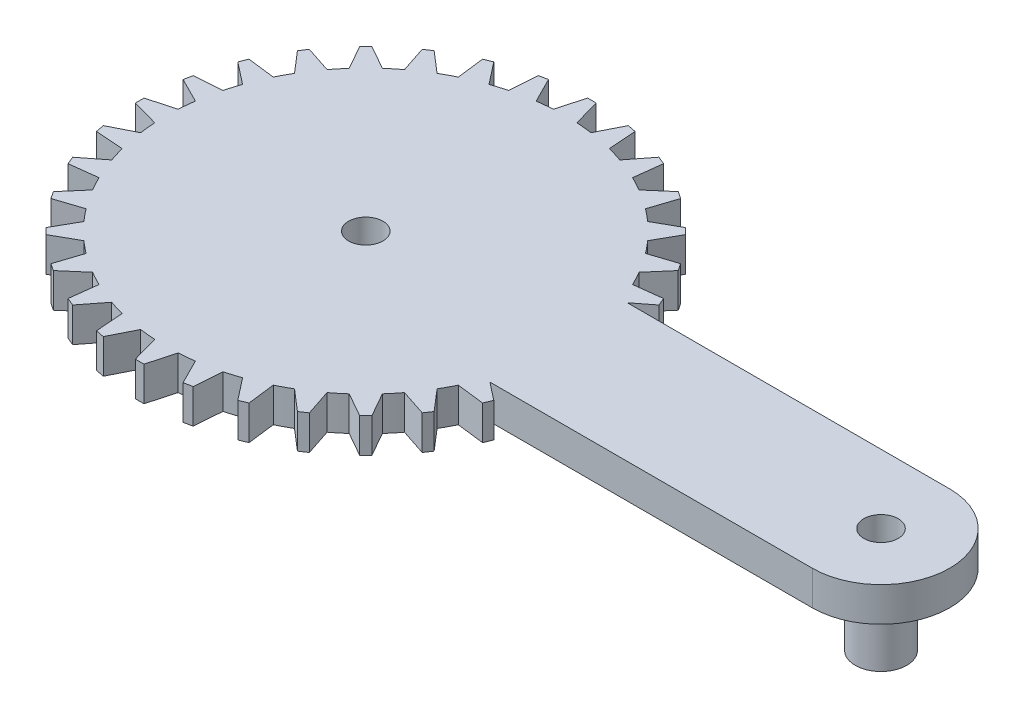
SolidWorks part; units mm, degrees
ref_plane "Front Plane" through (0, 0, 0) normal (0, 0, 1) x (1, 0, 0)
ref_plane "Top Plane" through (0, 0, 0) normal (0, 1, 0) x (1, 0, 0)
ref_plane "Right Plane" through (0, 0, 0) normal (1, 0, 0) x (0, 0, -1)
sketch "Sketch3" plane through (0, 0, 0) normal (0, 1, 0) x (1, 0, 0)
  circle A0 centre (0, 0) radius 2.5
  dimension "D1" = 5
extrude "Boss-Extrude1" add sketch "Sketch3" along normal blind 4.15
sketch "Sketch4" plane through (0, 4.15, 0) normal (0, 1, 0) x (1, 0, 0)
  line L0 (0, 0) -> (30, 0) construction
  line L1 (30, 4) -> (10.9152, 4)
  line L2 (30, -4) -> (10.9152, -4)
  arc A7 (10.9152, 4) -> (10.9152, -4) centre (0, 0) ccw
  arc A8 (30, -4) -> (30, 4) centre (30, 0) ccw
  circle A9 centre (30, 0) radius 1.5
  circle M1 centre (0, 0) radius 2.5
  dimension "D1" = 23.25
  dimension "D2" = 30
  dimension "D3" = 8
  dimension "D4" = 3
extrude "Boss-Extrude2" add sketch "Sketch4" along normal blind 2 contours M1 | A7 M1 | A8 L1 A7 L0 | A8 L0 A7 L2 | A8 region at (6.4096, 4.15, 0) region at (0, 4.15, 0)
extrude "Boss-Extrude3" add sketch "Sketch4<3>" along normal blind 2 contours A9 region at (30, 4.15, 0)
sketch "Sketch4<3>" plane through (0, 4.15, 0) normal (0, 1, 0) x (1, 0, 0) same geometry as "Sketch4"
extrude "Boss-Extrude4" add sketch "Sketch4<5>" against normal up to surface (4.15 mm away) contours A9 region at (30, 4.15, 0) up to face at (0, 0, 2.5)
sketch "Sketch4<5>" plane through (0, 4.15, 0) normal (0, 1, 0) x (1, 0, 0) same geometry as "Sketch4"
sketch "Sketch7" plane through (0, 6.15, 0) normal (0, 1, 0) x (1, 0, 0)
  line L0 (0, 0) -> (-12.7663, 0) construction
  line L1 (-12.7663, 0) -> (-11.3663, 0) construction
  line L2 (-11.3663, 0.75) -> (-11.3663, -0.75)
  line L3 (-13.1663, -0.25) -> (-13.1663, 0.25)
  line L4 (-13.1663, 0.25) -> (-11.3663, 0.75)
  line L5 (-11.3663, -0.75) -> (-13.1663, -0.25)
  point P6 (-11.3663, 0)
  point P9 (-13.1663, 0)
  dimension "D1" = 1.4
  dimension "D2" = 1.8
  dimension "D3" = 0.5
  dimension "D4" = 1.5
extrude "Boss-Extrude5" add sketch "Sketch7" against normal up to surface (2 mm away) up to face at (30, 4.15, 1.5)
pattern_circular "CirPattern1" count 32 over 360 about axis through (0, 4.15, 0) along (0, 1, 0) of "Boss-Extrude5"
sketch "Sketch8" plane through (0, 6.15, 0) normal (0, 1, 0) x (1, 0, 0)
  circle A0 centre (0, 0) radius 1
  circle A1 centre (30, 0) radius 1
  dimension "D1" = 2
  dimension "D2" = 2
extrude "Cut-Extrude1" cut sketch "Sketch8" against normal blind 10
